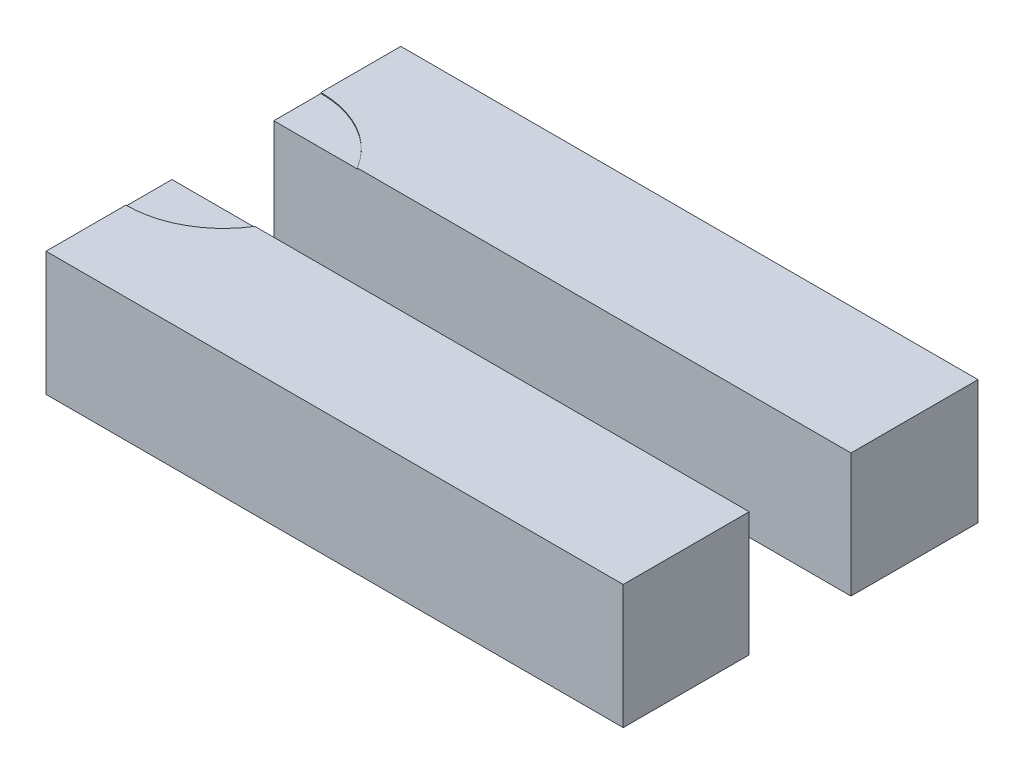
SolidWorks part; units mm, degrees
ref_plane "Front Plane" through (0, 0, 0) normal (0, 0, 1) x (1, 0, 0)
ref_plane "Top Plane" through (0, 0, 0) normal (0, 1, 0) x (1, 0, 0)
ref_plane "Right Plane" through (0, 0, 0) normal (1, 0, 0) x (0, 0, -1)
sketch "Sketch1" plane through (0, 0, 0) normal (0, 1, 0) x (1, 0, 0)
  line L1 (-41.3258, -12.7) -> (41.3258, -12.7)
  line L2 (-41.3258, -12.7) -> (-41.3258, 12.7)
  line L3 (-41.3258, 12.7) -> (41.3258, 12.7)
  line L4 (41.3258, -12.7) -> (41.3258, 12.7)
  line L5 (-41.3258, -12.7) -> (41.3258, 12.7) construction
  line L6 (-41.3258, 12.7) -> (41.3258, -12.7) construction
  point P0 (0, 0)
  dimension "D1" = 82.6516
  dimension "D2" = 25.4
extrude "Boss-Extrude1" add sketch "Sketch1" along normal blind 9.5758
sketch "Sketch2" plane through (0, 9.5758, 0) normal (0, 1, 0) x (1, 0, 0)
  line L0 (-9.4742, -3.683) -> (41.3258, -3.683)
  line L1 (-9.4742, -3.683) -> (-9.4742, 3.6068)
  line L2 (41.3258, -3.683) -> (41.3258, 3.6068)
  line L3 (-9.4742, 3.6068) -> (41.3258, 3.6068)
  line L4 (-9.4742, -3.683) -> (41.3258, 3.6068) construction
  line L5 (41.3258, -3.683) -> (-9.4742, 3.6068) construction
  line L6 (-41.3258, -12.7) -> (41.3258, -12.7) construction
  line L7 (41.3258, 12.7) -> (-41.3258, 12.7) construction
  point P1 (15.9258, -0.0381)
  dimension "D1" = 7.2898
  dimension "D2" = 50.8
  dimension "D3" = 9.017
  dimension "D4" = 9.0932
extrude "Cut-Extrude1" cut sketch "Sketch2" against normal through all
sketch "Sketch8" plane through (0, 0, 12.7) normal (0, 0, 1) x (1, 0, 0)
  line L1 (0, 0) -> (-2.9028, 0)
  line L2 (0, 0) -> (0, 9.5801)
  line L3 (0, 9.5801) -> (-2.9028, 9.5801)
  line L4 (-2.9028, 0) -> (-2.9028, 9.5801)
extrude "Boss-Extrude4" add sketch "Sketch8" against normal through all
sketch "Sketch10" plane through (0, 9.5758, 0) normal (0, 1, 0) x (1, 0, 0)
  circle A0 centre (0, 0) radius 12.7
extrude "Boss-Extrude5" add sketch "Sketch10" along normal blind 50.1015
sketch "Sketch12" plane through (0, 59.6773, 0) normal (0, 1, 0) x (1, 0, 0)
  circle A0 centre (0, 0) radius 6.985
  dimension "D1" = 13.97
extrude "Cut-Extrude2" cut sketch "Sketch12" against normal blind 50.8635
chamfer "Chamfer1" distance 2.54 angle 45 1 edges at (0, 59.6773, 12.7)
ref_plane "Plane1" through (0, 0, -6.985) normal (0, 0, 1) x (1, 0, 0)
sketch "Sketch14" plane through (0, 0, -6.985) normal (0, 0, 1) x (1, 0, 0)
  line L1 (6.35, 29.0908) -> (-6.35, 29.0908)
  line L2 (6.35, 29.0908) -> (6.35, 54.4908)
  line L3 (6.35, 54.4908) -> (-6.35, 54.4908)
  line L4 (-6.35, 29.0908) -> (-6.35, 54.4908)
  line L5 (6.35, 29.0908) -> (-6.35, 54.4908) construction
  line L6 (6.35, 54.4908) -> (-6.35, 29.0908) construction
  point P0 (0, 41.7908)
  dimension "D1" = 12.7
  dimension "D2" = 25.4
extrude "Boss-Extrude6" add sketch "Sketch14" against normal blind 15.24
sketch "Sketch18" plane through (6.35, 0, 0) normal (1, 0, 0) x (0, 0, -1)
  line L1 (13.2284, 39.2508) -> (19.0704, 39.2508)
  line L2 (13.2284, 39.2508) -> (13.2284, 50.6808)
  line L3 (13.2284, 50.6808) -> (19.0704, 50.6808)
  line L4 (19.0704, 39.2508) -> (19.0704, 50.6808)
  line L5 (13.2284, 39.2508) -> (19.0704, 50.6808) construction
  line L6 (13.2284, 50.6808) -> (19.0704, 39.2508) construction
  line L7 (22.225, 54.4908) -> (10.9985, 54.4908) construction
  point P0 (16.1494, 44.9658)
  dimension "D1" = 11.43
  dimension "D2" = 5.842
  dimension "D3" = 3.81
  dimension "D4" = 3.81
extrude "Cut-Extrude3" cut sketch "Sketch18" against normal up to next
hole_wizard "1/4 Clearance Hole2" positions "Sketch20" profile "Sketch19" hole size "1/4" standard "ANSI Inch"
sketch "Sketch20" plane through (0, 0, -22.225) normal (0, 0, -1) x (-1, 0, 0)
  line L0 (6.35, 54.4908) -> (-6.35, 54.4908) construction
  line L1 (-6.35, 29.0908) -> (6.35, 29.0908) construction
  point P0 (0, 44.9658)
  dimension "D1" = 9.525
  dimension "D2" = 15.875
sketch "Sketch19" plane through (0, 44.9658, -22.225) normal (1, 0, 0) x (0, 1, 0)
  line L0 (0, 0) -> (0, 22.3498)
  line L1 (0, 22.3498) -> (3.3782, 20.32)
  line L2 (3.3782, 20.32) -> (3.3782, 0)
  line L5 (3.3782, 0) -> (0, 0)
  line L10 (0, 22.3498) -> (-3.3782, 20.32) construction
  line L11 (0, -6.35) -> (0, 107.95) construction
  dimension "Hole Dia." = 6.7564
  dimension "Hole Depth" = 20.32
  dimension "Drill Angle" = 118
chamfer "Chamfer2" distance 10.16 angle 45 1 edges at (0, 29.0908, -22.225)
sketch "Sketch21" plane through (0, 59.6773, 0) normal (0, 1, 0) x (1, 0, 0)
  line L1 (-52.2341, 32.5275) -> (49.937, 32.5275)
  line L2 (-52.2341, 32.5275) -> (-52.2341, -26.4981)
  line L3 (-52.2341, -26.4981) -> (49.937, -26.4981)
  line L4 (49.937, 32.5275) -> (49.937, -26.4981)
extrude "Cut-Extrude4" cut sketch "Sketch21" against normal blind 50.8
sketch "Sketch22" plane through (0, 0, 0) normal (1, 0, 0) x (0, 0, -1)
  line L1 (16.4624, 11.6654) -> (-17.2995, 11.6654)
  line L2 (16.4624, 11.6654) -> (16.4624, -3.6252)
  line L3 (16.4624, -3.6252) -> (-17.2995, -3.6252)
  line L4 (-17.2995, 11.6654) -> (-17.2995, -3.6252)
extrude "Cut-Extrude5" cut sketch "Sketch22" against normal through all
